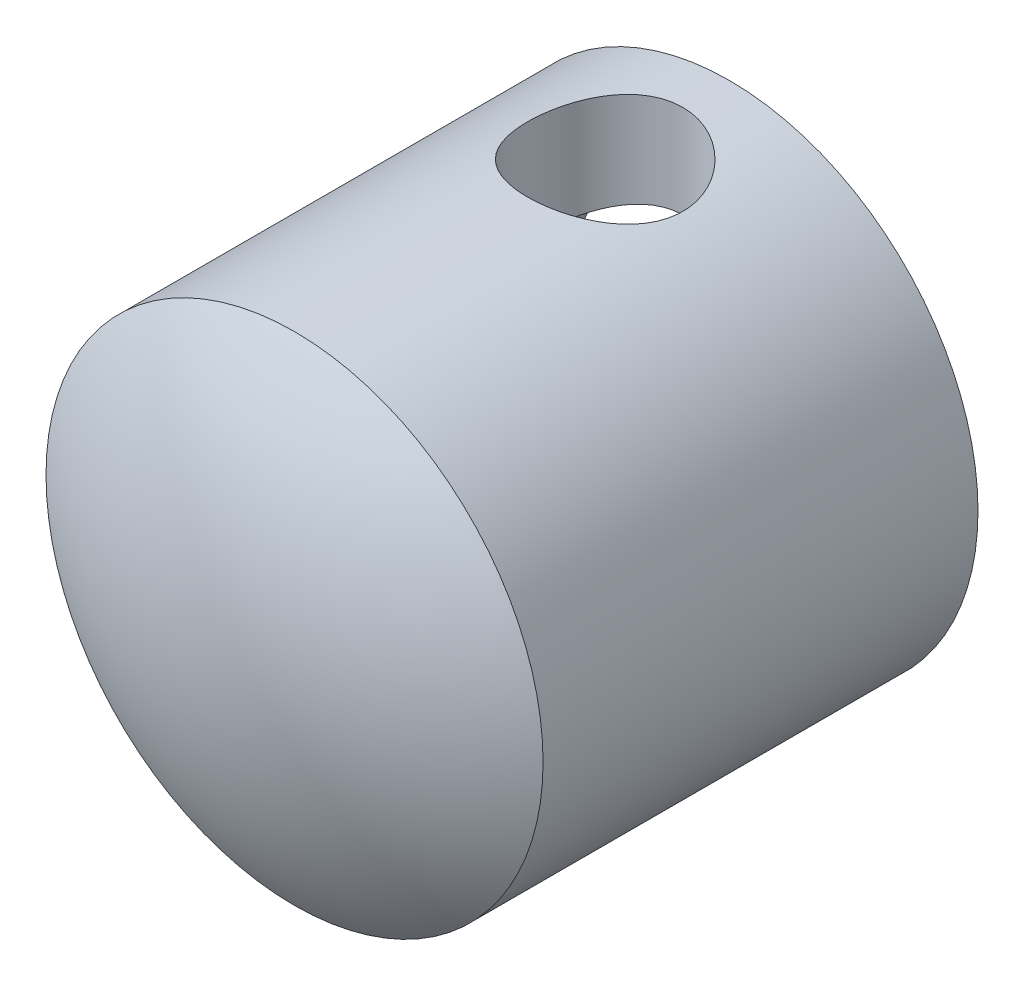
SolidWorks part; units mm, degrees
ref_plane "Face" through (0, 0, 0) normal (0, 0, 1) x (1, 0, 0)
ref_plane "zzzzz" through (0, 0, 0) normal (0, 1, 0) x (1, 0, 0)
ref_plane "Droite" through (0, 0, 0) normal (1, 0, 0) x (0, 0, -1)
ref_axis "Axe1" through (0, 0, 50) along (0, 0, -1)
sketch "Esquisse2" plane through (0, 0, 0) normal (1, 0, 0) x (0, 0, -1)
  line L0 (-63.5, 5) -> (-73.5, 5)
  line L1 (-73.5, 5) -> (-73.5, 4)
  line L2 (-73.5, 4) -> (-74.5, 4)
  line L3 (-74.5, 4) -> (-77.4104, 0)
  line L4 (-63.5, 5) -> (-63.5, 8)
  line L5 (-63.5, 8) -> (-77.5, 8)
  line L6 (-77.4104, 0) -> (-80.0109, 0)
  line L7 (-77.4104, 0) -> (-40.8548, 0) construction
  line L8 (-72.5, 4.5) -> (-72.5, -4.5) construction
  line L10 (0, 0) -> (-19.0216, 0) construction
  arc A0 (-77.5, 8) -> (-80.0109, 0) centre (-66.0109, 0) ccw
  dimension "D6" = 14
  dimension "D1" = 3
  dimension "D2" = 10
  dimension "D3" = 2.6005
  dimension "D4" = 14
  dimension "D5" = 1
  dimension "D7" = 1
  dimension "D8" = 1
revolve "Base-Révolution" add sketch "Esquisse2" angle 360 about L10
sketch "Esquisse3" plane through (0, 0, 0) normal (0, 1, 0) x (1, 0, 0)
  circle A0 centre (0, -67.5) radius 2.5
  circle A1 centre (0, -67.5) radius 2.5 construction
extrude "Enlèv. mat.-Extru.1" cut sketch "Esquisse3" against normal mid plane 20
